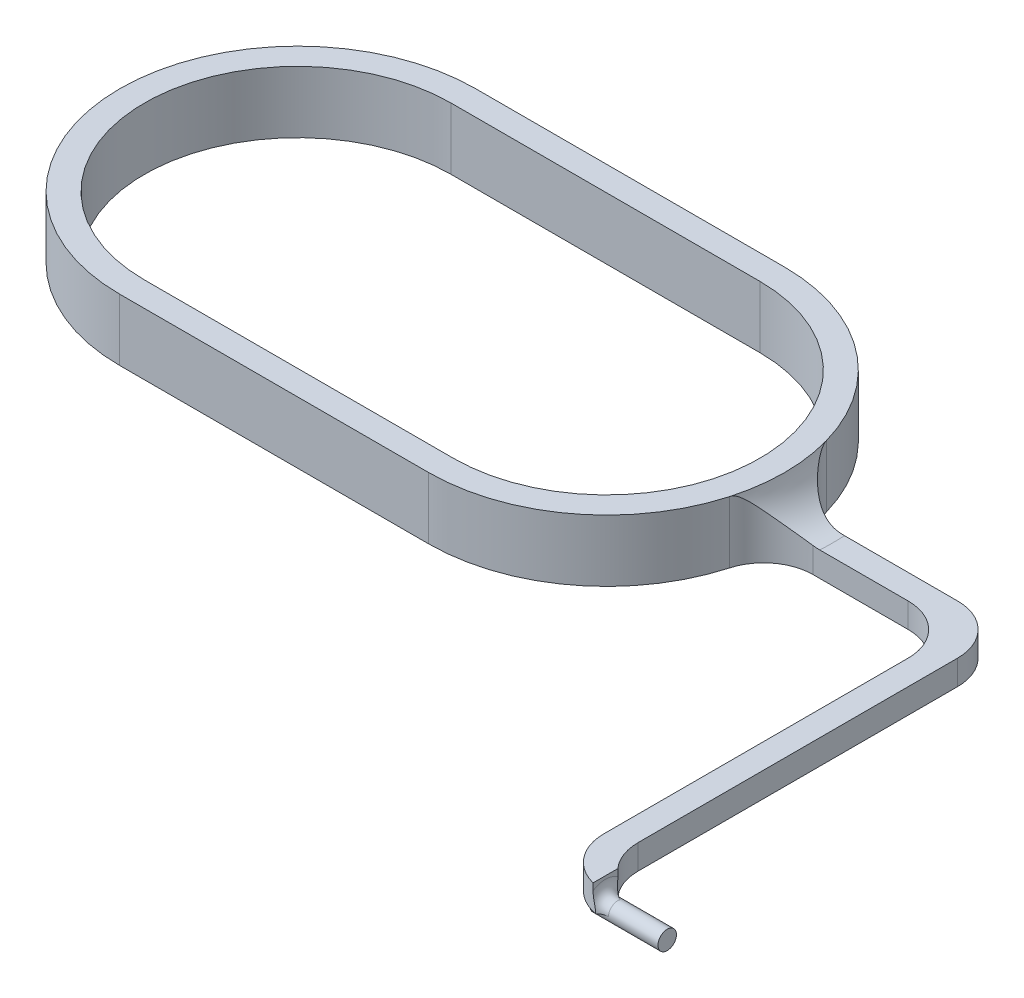
SolidWorks part; units mm, degrees
ref_plane "Front Plane" through (0, 0, 0) normal (0, 0, 1) x (1, 0, 0)
ref_plane "Top Plane" through (0, 0, 0) normal (0, 1, 0) x (1, 0, 0)
ref_plane "Right Plane" through (0, 0, 0) normal (1, 0, 0) x (0, 0, -1)
sketch "Sketch1" plane through (0, 0, 0) normal (0, 1, 0) x (1, 0, 0)
  line L0 (0, 0) -> (25, 0) construction
  line L1 (0, 12.4) -> (25, 12.4)
  line L2 (0, -12.4) -> (25, -12.4)
  line L3 (0, 0) -> (25, 0) construction
  line L4 (0, 14.4) -> (25, 14.4)
  line L5 (0, -14.4) -> (25, -14.4)
  arc A0 (0, 12.4) -> (0, -12.4) centre (0, 0) ccw
  arc A1 (25, -12.4) -> (25, 12.4) centre (25, 0) ccw
  arc A2 (0, 14.4) -> (0, -14.4) centre (0, 0) ccw
  arc A3 (25, -14.4) -> (25, 14.4) centre (25, 0) ccw
  point P3 (12.5, 0)
  point P10 (12.5, 0)
  dimension "D1" = 24.8
  dimension "D2" = 25
  dimension "D3" = 2
extrude "Boss-Extrude1" add sketch "Sketch1" along normal blind 5
sketch "Sketch2" plane through (0, 0, 0) normal (0, -1, 0) x (1, 0, 0)
  line L1 (37.4, -1) -> (56.4, -1)
  line L2 (37.4, -1) -> (37.4, 1)
  line L3 (37.4, 1) -> (56.4, 1)
  line L4 (56.4, -1) -> (56.4, 1)
  line L5 (56.4, -1) -> (54.4, -1)
  line L6 (56.4, -1) -> (56.4, 33.5)
  line L7 (56.4, 33.5) -> (54.4, 33.5)
  line L8 (54.4, -1) -> (54.4, 33.5)
  line L9 (54.4, 33.5) -> (57.4, 33.5)
  line L10 (54.4, 33.5) -> (54.4, 31.5)
  line L11 (54.4, 31.5) -> (57.4, 31.5)
  line L12 (57.4, 33.5) -> (57.4, 31.5)
  arc A0 (25, -12.4) -> (25, 12.4) centre (25, 0) ccw construction
  arc A1 (25, -14.4) -> (25, 14.4) centre (25, 0) ccw construction
  point P10 (37.4, 0)
  point P18 (39.4, 0)
  point P19 (57.4, 32.5)
  arc M13 (25, -14.4) -> (25, 14.4) centre (25, 0) ccw
  dimension "D1" = 15
  dimension "D2" = 2
  dimension "D3" = 2
  dimension "D4" = 2
  dimension "D5" = 32.5
  dimension "D6" = 1
extrude "Boss-Extrude2" add sketch "Sketch2" against normal blind 2 contours L12 L9 L6 L11 | L8 L11 L6 L7 | L11 L8 L3 L6 | L1 L8 L3 M13 | L8 L1 L4 L3 | L3 L2 L1 M13 region at (55.4, 0, 0) region at (46.8942, 0, 0) region at (38.3942, 0, 0) region at (55.4, 0, 16.25) region at (55.4, 0, 32.5) region at (56.9, 0, 32.5)
fillet "Fillet1" radius 4 7 edges at (39.4, 2, 0) (39.3652, 1, 1) (39.3652, 1, -1) (56.4, 1, -1) (54.4, 1, 1) (54.4, 1, 33.5) (56.4, 1, 31.5)
sketch "Sketch3" plane through (57.4, 0, 0) normal (1, 0, 0) x (0, 0, -1)
  line L1 (-33.5, 0) -> (-31.5, 0) construction
  circle A0 centre (-32.5, 0) radius 0.75
  point P8 (-32.5, 0)
  dimension "D1" = 1.5
extrude "Boss-Extrude3" add sketch "Sketch3" along normal blind 5 and the other way blind 0.5 contours A0
fillet "Fillet3" radius 1 1 edges at (57.4, 0.75, 32.5)
